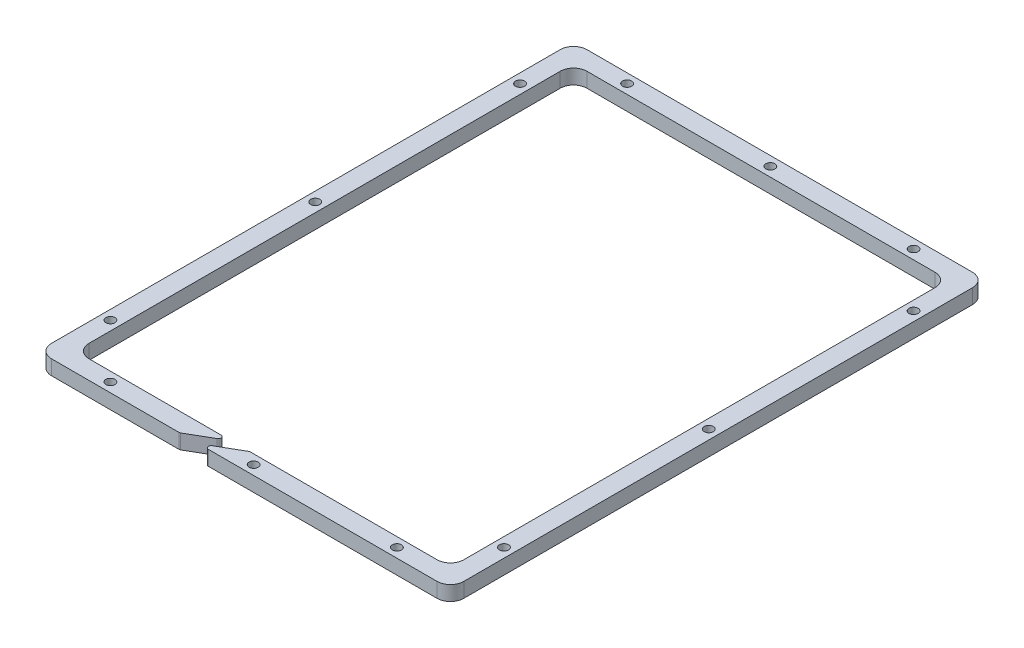
SolidWorks part; units mm, degrees
ref_plane "Front Plane" through (0, 0, 0) normal (0, 0, 1) x (1, 0, 0)
ref_plane "Top Plane" through (0, 0, 0) normal (0, 1, 0) x (1, 0, 0)
ref_plane "Right Plane" through (0, 0, 0) normal (1, 0, 0) x (0, 0, -1)
sketch "Sketch1" plane through (0, 0, 0) normal (0, 1, 0) x (1, 0, 0)
  line L0 (-80, 101) -> (-80, -101) construction
  line L1 (-70, -93) -> (70, -93)
  line L2 (-70, -93) -> (-70, 93)
  line L3 (-70, 93) -> (70, 93)
  line L4 (70, -93) -> (70, 93)
  line L5 (-70, -93) -> (70, 93) construction
  line L6 (-70, 93) -> (70, -93) construction
  line L7 (77, -100) -> (-77, -100)
  line L8 (77, -100) -> (77, 100)
  line L9 (77, 100) -> (-77, 100)
  line L10 (-77, -100) -> (-77, 100)
  line L11 (77, -100) -> (-77, 100) construction
  line L12 (77, 100) -> (-77, -100) construction
  line L13 (-78, -103) -> (78, -103) construction
  line L14 (68, 93) -> (-68, 93) construction
  line L15 (-70, 91) -> (-70, -91) construction
  point P0 (0, 0)
  point P5 (0, 0)
  dimension "D3" = 3
  dimension "D4" = 3
extrude "Boss-Extrude1" add sketch "Sketch1" along normal blind 5.5
ref_axis "Axis2" through (0, -0.3, 0) along (0, 1, 0)
fillet "Fillet1" radius 5 8 edges at (77, 2.75, -100) (77, 2.75, 100) (-77, 2.75, -100) (-77, 2.75, 100) (70, 2.75, -93) (70, 2.75, 93) (-70, 2.75, 93) (-70, 2.75, -93)
ref_plane "Plane1" through (0, 2.75, 0) normal (0, 1, 0) x (1, 0, 0)
sketch "Sketch3" plane through (0, 0, 0) normal (0, -1, 0) x (1, 0, 0)
  line L0 (0, 100) -> (0, 96.5) construction
  line L1 (73.5, 96.5) -> (-73.5, 96.5) construction
  line L2 (73.5, 96.5) -> (73.5, -96.5) construction
  line L3 (73.5, -96.5) -> (-73.5, -96.5) construction
  line L4 (-73.5, 96.5) -> (-73.5, -96.5) construction
  line L5 (-72, 100) -> (72, 100) construction
  line L6 (0, 96.5) -> (0, 93) construction
  line L7 (-65, 93) -> (65, 93) construction
  line L8 (77, 0) -> (73.5, 0) construction
  line L9 (77, 95) -> (77, -95) construction
  line L10 (73.5, 0) -> (70, 0) construction
  line L11 (70, 88) -> (70, -88) construction
  line L12 (-70, 0) -> (-73.5, 0) construction
  line L13 (-70, -88) -> (-70, 88) construction
  line L14 (0, -96.5) -> (0, -93) construction
  line L15 (65, -93) -> (-65, -93) construction
  circle A0 centre (73.5, -76.5) radius 1.7
  circle A1 centre (53.5, -96.5) radius 1.7
  circle A2 centre (-53.5, -96.5) radius 1.7
  circle A3 centre (-73.5, -76.5) radius 1.7
  circle A4 centre (-73.5, 0) radius 1.7
  circle A5 centre (-73.5, 76.5) radius 1.7
  circle A6 centre (-53.5, 96.5) radius 1.7
  circle A7 centre (53.5, 96.5) radius 1.7
  circle A8 centre (73.5, 76.5) radius 1.7
  circle A9 centre (73.5, 0) radius 1.7
  circle A10 centre (0, -96.5) radius 1.7
  circle A11 centre (0, 96.5) radius 1.7
  dimension "D1" = 3.4
  dimension "D5" = 73.5
  dimension "D2" = 96.5
  dimension "D3" = 20
  dimension "D4" = 20
  dimension "D6" = 20
  dimension "D7" = 20
extrude "Cut-Extrude1" cut sketch "Sketch3" against normal through all
sketch "Sketch4" plane through (0, 5.5, 0) normal (0, 1, 0) x (1, 0, 0)
  line L0 (-17.1244, -100) -> (-5, -93)
  line L1 (-72, -100) -> (72, -100) construction
  line L2 (-65, -93) -> (65, -93) construction
  line L3 (-12, -93) -> (-5, -93)
  line L4 (-24.1244, -100) -> (-12, -93)
  line L5 (-24.1244, -100) -> (-17.1244, -100)
  circle A0 centre (0, -96.5) radius 1.7 construction
  point P6 (-6.2362, -93)
  point P9 (-24.3991, -100)
  dimension "D1" = 3.5
  dimension "D2" = 30
  dimension "D3" = 5
extrude "Cut-Extrude2" cut sketch "Sketch4" against normal through all
fillet "Fillet2" radius 1 4 edges at (-24.1244, 2.75, 100) (-12, 2.75, 93) (-5, 2.75, 93) (-17.1244, 2.75, 100)
